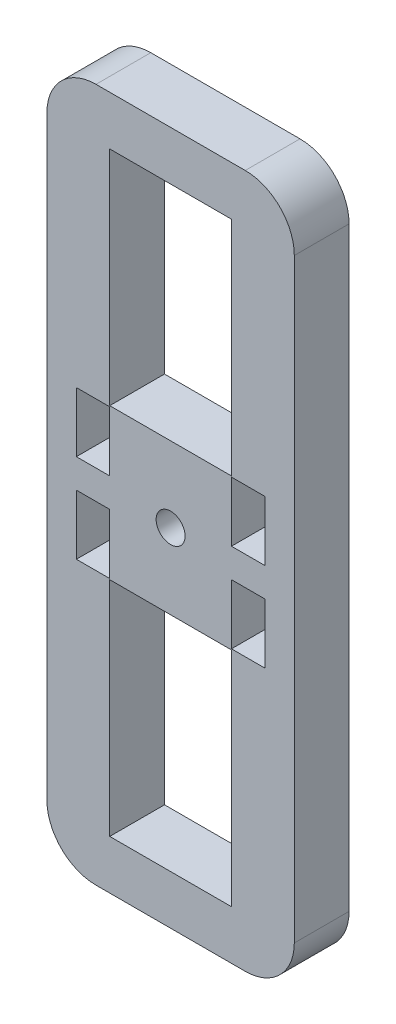
SolidWorks part; units mm, degrees
material "Acrylic (Medium-high impact)"
ref_plane "Front Plane" through (0, 0, 0) normal (0, 0, 1) x (1, 0, 0)
ref_plane "Top Plane" through (0, 0, 0) normal (0, 1, 0) x (1, 0, 0)
ref_plane "Right Plane" through (0, 0, 0) normal (1, 0, 0) x (0, 0, -1)
sketch "Sketch1" plane through (0, 0, 0) normal (0, 0, 1) x (1, 0, 0)
  line L0 (709.4957, 498.2797) -> (721.8957, 498.2797)
  line L1 (721.8957, 498.2797) -> (721.8957, 475.6297)
  line L2 (721.8957, 475.6297) -> (709.4957, 475.6297)
  line L3 (709.4957, 475.6297) -> (709.4957, 498.2797)
  line L4 (715.6957, 432.6297) -> (723.2957, 432.6297)
  line L5 (715.6957, 503.2797) -> (708.0957, 503.2797)
  line L6 (715.6957, 503.2797) -> (723.2957, 503.2797)
  line L7 (715.6957, 460.2797) -> (715.6957, 475.6297) construction
  line L8 (709.4957, 498.2797) -> (703.0957, 498.2797) construction
  line L9 (721.8957, 498.2797) -> (728.2957, 498.2797) construction
  line L10 (709.4957, 475.5297) -> (706.0957, 475.5297)
  line L11 (728.2957, 498.2797) -> (728.2957, 437.6297)
  line L12 (709.4957, 475.5297) -> (709.4957, 469.4297)
  line L13 (709.4957, 469.4297) -> (706.0957, 469.4297)
  line L14 (706.0957, 469.4297) -> (706.0957, 475.5297)
  line L15 (703.0957, 498.2797) -> (703.0957, 437.6297)
  line L16 (721.8957, 475.5297) -> (725.2957, 475.5297)
  line L17 (725.2957, 469.4297) -> (725.2957, 475.5297)
  line L18 (721.8957, 469.4297) -> (725.2957, 469.4297)
  line L19 (721.8957, 475.5297) -> (721.8957, 469.4297)
  line L20 (721.8957, 460.3797) -> (725.2957, 460.3797)
  line L21 (725.2957, 466.4797) -> (725.2957, 460.3797)
  line L22 (715.6957, 432.6297) -> (708.0957, 432.6297)
  line L24 (721.8957, 466.4797) -> (725.2957, 466.4797)
  line L25 (721.8957, 460.3797) -> (721.8957, 466.4797)
  line L26 (709.4957, 460.3797) -> (706.0957, 460.3797)
  line L27 (706.0957, 466.4797) -> (706.0957, 460.3797)
  line L28 (709.4957, 466.4797) -> (706.0957, 466.4797)
  line L29 (709.4957, 460.3797) -> (709.4957, 466.4797)
  line L30 (-282.9616, 469.4297) -> (49717.0384, 469.4297) construction
  line L31 (-282.9616, 466.4797) -> (49717.0384, 466.4797) construction
  line L37 (709.4957, 460.2797) -> (709.4957, 437.6297)
  line L38 (721.8957, 460.2797) -> (709.4957, 460.2797)
  line L39 (721.8957, 437.6297) -> (721.8957, 460.2797)
  line L40 (709.4957, 437.6297) -> (721.8957, 437.6297)
  line L171 (-296.4722, 467.9547) -> (49703.5278, 467.9547) construction
  circle A0 centre (715.6957, 467.9547) radius 1.475
  arc A1 (708.0957, 432.6297) -> (703.0957, 437.6297) centre (708.0957, 437.6297) cw
  arc A2 (708.0957, 503.2797) -> (703.0957, 498.2797) centre (708.0957, 498.2797) ccw
  arc A3 (723.2957, 503.2797) -> (728.2957, 498.2797) centre (723.2957, 498.2797) cw
  arc A4 (723.2957, 432.6297) -> (728.2957, 437.6297) centre (723.2957, 437.6297) ccw
  point P6 (715.6957, 504.6992)
  point P33 (715.6957, 475.6297)
  point P37 (715.6957, 467.9547)
  point P46 (715.6957, 431.2102)
  dimension "D1" = 6.1
  dimension "D4" = 2.95
  dimension "D2" = 3.4
  dimension "D3" = 0.1
  dimension "D5" = 22.65
  dimension "D6" = 12.4
  dimension "D7" = 3
  dimension "D8" = 5
extrude "Boss-Extrude1" add sketch "Sketch1" along normal blind 5.58 contours L2 L3 L0 L1 L40 L37 L38 L39 A0 region at (711.8957, 433.3798, 0)
